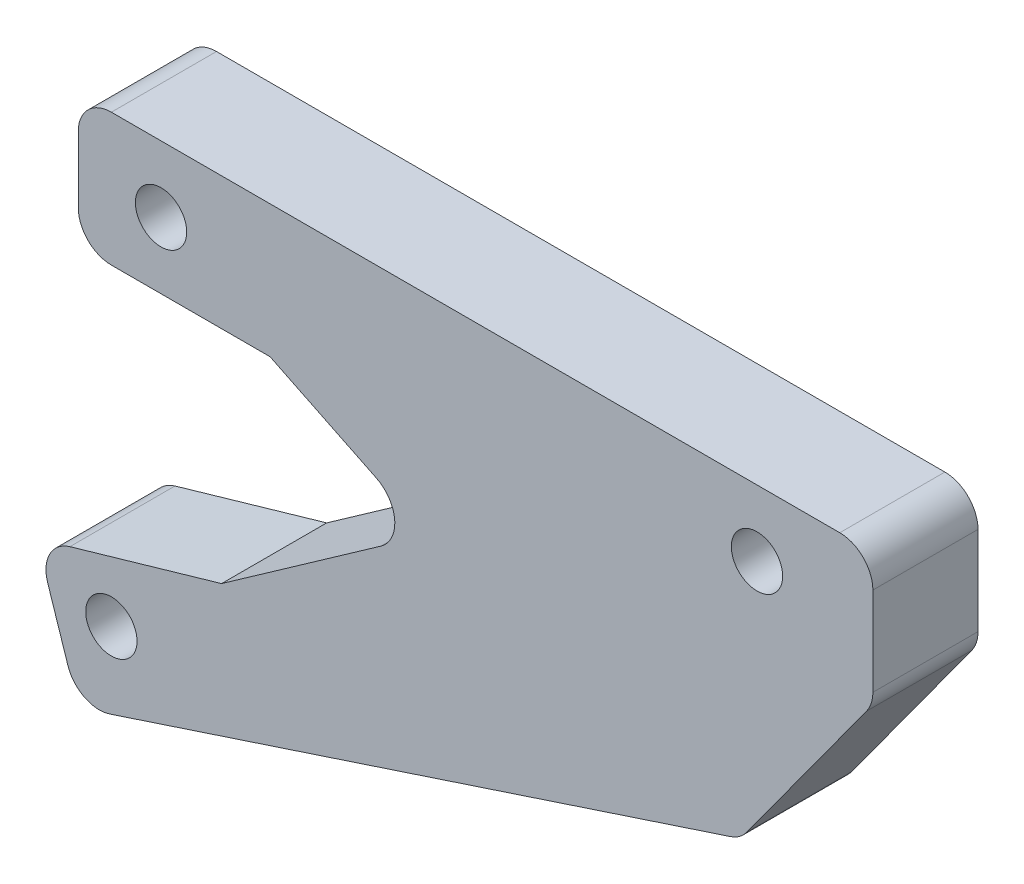
SolidWorks part; units mm, degrees
ref_plane "Front Plane" through (0, 0, 0) normal (0, 0, 1) x (1, 0, 0)
ref_plane "Top Plane" through (0, 0, 0) normal (0, 1, 0) x (1, 0, 0)
ref_plane "Right Plane" through (0, 0, 0) normal (1, 0, 0) x (0, 0, -1)
sketch "Sketch1" plane through (0, 0, 0) normal (0, 0, 1) x (1, 0, 0)
  line L5 (24, -4) -> (16, -15)
  line L6 (-24, 4) -> (24, 4)
  line L12 (-24, 4) -> (-24, -4)
  line L13 (-24, -4) -> (14, -4)
  line L14 (24, 4) -> (24, -4)
  line L15 (-24, 4) -> (24, -4) construction
  line L16 (-24, -4) -> (24, 4) construction
  line L17 (16, -15) -> (-24, -28.159)
  line L18 (-24, -28.159) -> (-26.5, -20.5597)
  line L19 (-26.5, -20.5597) -> (10, -10)
  line L20 (10, -10) -> (14, -4)
  line L21 (14, -4) -> (24, -4) construction
  point P0 (0, 0)
  point P2 (0, 0)
  dimension "D1" = 8
  dimension "D2" = 48
  dimension "D3" = 10
  dimension "D4" = 14
  dimension "D5" = 8
  dimension "D6" = 8
  dimension "D7" = 40.5
  dimension "D8" = 6
  dimension "D9" = 11
  dimension "D10" = 40
extrude "Boss-Extrude1" add sketch "Sketch1" along normal blind 6.35
sketch "Sketch2" plane through (0, 0, 0) normal (0, 0, 1) x (1, 0, 0)
  line L0 (10, -10) -> (-26.5, -20.5597) construction
  circle A0 centre (-19, 0) radius 1.55
  circle A1 centre (17, 0) radius 1.55
  circle A2 centre (-22, -22.9013) radius 1.55
  dimension "D1" = 3.1
  dimension "D2" = 3.1
  dimension "D3" = 3.1
  dimension "D4" = 17
  dimension "D5" = 19
  dimension "D6" = 22
  dimension "D7" = 3.5
extrude "Cut-Extrude3" cut sketch "Sketch2" against normal through all and the other way through all
ref_axis "Axis1" through (10, -10, 6.35) along (0.7682, -0.6402, 0)
sketch "Sketch3" plane through (0, 0, 6.35) normal (0, 0, 1) x (1, 0, 0)
  line L0 (-12.4164, -4) -> (14, -4)
  line L1 (-24, -4) -> (14, -4) construction
  line L2 (14, -4) -> (10, -10)
  line L3 (10, -10) -> (-15.3429, -17.3319)
  line L4 (10, -10) -> (-26.5, -20.5597) construction
  line L6 (-12.4164, -4) -> (-2.9585, -8.6177)
  line L7 (-2.9585, -8.6177) -> (-15.3429, -17.3319)
extrude "Boss-Extrude2" add sketch "Sketch3" against normal up to surface (6.35 mm away) up to face at (-20.45, -22.9013, 0)
fillet "Fillet1" radius 2 8 edges at (-24, 4, 3.175) (-24, -4, 3.175) (-26.5, -20.5597, 3.175) (-24, -28.159, 3.175) (16, -15, 3.175) (24, -4, 3.175) (24, 4, 3.175) (-2.9585, -8.6177, 3.175)
equation "\"ScrewSize\"= 3.1mm"
